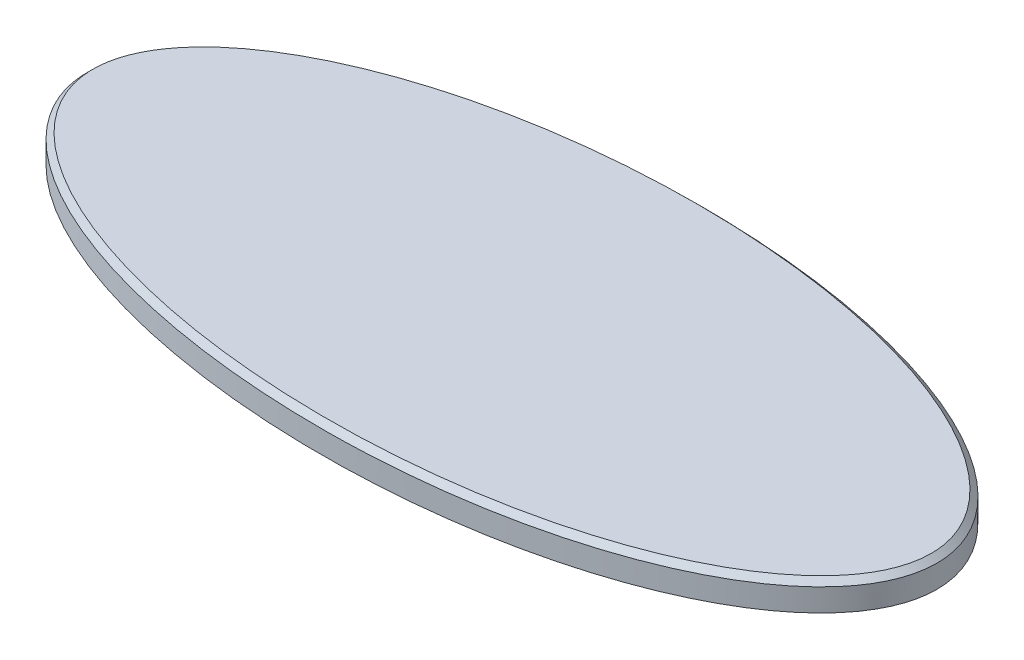
SolidWorks part; units mm, degrees
ref_plane "Front Plane" through (0, 0, 0) normal (0, 0, 1) x (1, 0, 0)
ref_plane "Top Plane" through (0, 0, 0) normal (0, 1, 0) x (1, 0, 0)
ref_plane "Right Plane" through (0, 0, 0) normal (1, 0, 0) x (0, 0, -1)
sketch "Sketch1" plane through (0, 0, 0) normal (0, 1, 0) x (1, 0, 0)
  line L0 (-150, 0) -> (150, 0) construction
  ellipse E0 centre (0, 0) end of major axis (150, 0) minor radius 67.5
  dimension "D1" = 300
  dimension "D2" = 135
extrude "Boss-Extrude1" add sketch "Sketch1" along normal blind 10 contours E0
chamfer "Chamfer1" distance 2 1 edges at (150, 10, 0)
